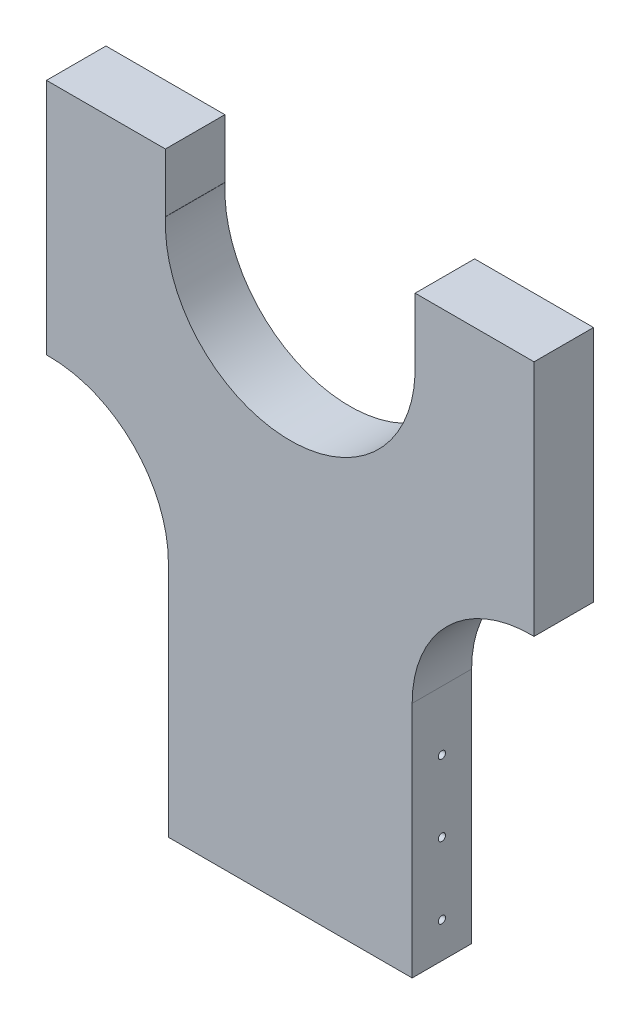
SolidWorks part; units mm, degrees
ref_plane "Front Plane" through (0, 0, 0) normal (0, 0, 1) x (1, 0, 0)
ref_plane "Top Plane" through (0, 0, 0) normal (0, 1, 0) x (1, 0, 0)
ref_plane "Right Plane" through (0, 0, 0) normal (1, 0, 0) x (0, 0, -1)
sketch "Sketch1" plane through (0, 0, 0) normal (0, 0, 1) x (1, 0, 0)
  line L0 (0, 0) -> (0, 99.9478) construction
  line L1 (0, 0) -> (-105.839, 0) construction
  line L2 (-142.7762, 400) -> (240.224, 400) construction
  line L7 (-92.5182, 500) -> (259.2874, 500) construction
  line L8 (-102.5, 485.4345) -> (-102.5, -62.3793) construction
  line L9 (-205, 425.4562) -> (-205, 156.6078) construction
  line L10 (-358.1139, 300) -> (-64.3941, 300) construction
  line L11 (102.5, 0) -> (-102.5, 0)
  line L12 (-102.5, 0) -> (-102.5, 200)
  line L13 (-202.5, 300) -> (-205, 300)
  line L14 (-205, 300) -> (-205, 490)
  line L15 (-195, 500) -> (-112.5, 500)
  line L16 (-102.5, 490) -> (-102.5, 400.25)
  line L17 (-102.25, 400) -> (102.25, 400)
  line L18 (102.5, 490) -> (102.5, 400.25)
  line L19 (195, 500) -> (112.5, 500)
  line L20 (205, 300) -> (205, 490)
  line L21 (202.5, 300) -> (205, 300)
  line L22 (102.5, 0) -> (102.5, 200)
  arc A0 (102.5, 200) -> (202.5, 300) centre (202.5, 200) cw
  arc A1 (-102.5, 200) -> (-202.5, 300) centre (-202.5, 200) ccw
  arc A2 (205, 490) -> (195, 500) centre (195, 490) ccw
  arc A3 (112.5, 500) -> (102.5, 490) centre (112.5, 490) ccw
  arc A4 (-102.5, 490) -> (-112.5, 500) centre (-112.5, 490) ccw
  arc A5 (-195, 500) -> (-205, 490) centre (-195, 490) ccw
  arc A6 (102.25, 400) -> (102.5, 400.25) centre (102.25, 400.25) ccw
  arc A7 (-102.25, 400) -> (-102.5, 400.25) centre (-102.25, 400.25) cw
  point P24 (0, 400)
  point P29 (0, 0)
  point P31 (102.5, 300)
  point P34 (-102.5, 300)
  point P37 (205, 500)
  point P40 (102.5, 500)
  point P43 (-102.5, 500)
  point P46 (-205, 500)
  point P49 (102.5, 400)
  point P52 (-102.5, 400)
  dimension "D6" = 100
  dimension "D7" = 10
  dimension "D8" = 0.25
  dimension "D1" = 400
  dimension "D2" = 100
  dimension "D3" = 102.5
  dimension "D4" = 102.5
  dimension "D5" = 100
extrude "Boss-Extrude2" add sketch "Sketch1" along normal blind 50
sketch "Sketch2" plane through (0, 0, 0) normal (1, 0, 0) x (0, 0, -1)
  line L0 (0, 0) -> (-185.943, 0) construction
  line L1 (0, 0) -> (0, -33.187) construction
  line L2 (-137.4157, 30) -> (59.3527, 30) construction
  line L3 (-134.7567, 60) -> (60.0175, 60) construction
  line L4 (-143.7005, 90) -> (95.8999, 90) construction
  line L5 (-138.1489, 120) -> (60.2857, 120) construction
  line L6 (-100, 469.161) -> (-100, 561.3071) construction
  line L8 (-25, 355.6073) -> (-25, 534.3148) construction
  line L9 (-116.4868, 150) -> (33.8347, 150) construction
  circle A0 centre (-25, 30) radius 3.05
  circle A1 centre (-25, 90) radius 3.05
  circle A2 centre (-25, 150) radius 3.05
  point P2 (0, 0)
  point P26 (0, 0)
  point P27 (0, 0)
  dimension "D8" = 6.1
  dimension "D9" = 6.1
  dimension "D10" = 6.1
  dimension "D1" = 30
  dimension "D2" = 30
  dimension "D3" = 30
  dimension "D4" = 30
  dimension "D5" = 100
  dimension "D6" = 75
  dimension "D7" = 30
sketch "Sketch5" plane through (0, 0, 0) normal (0, 0, 1) x (1, 0, 0)
  line L0 (0, 0) -> (0, 495.9267) construction
  line L1 (0, 0) -> (-201.2141, 0) construction
  line L2 (-102.5, 445.125) -> (213.1937, 445.125) construction
  circle A0 centre (0, 445.125) radius 105
  point P10 (0, 0)
  dimension "D2" = 210
  dimension "D1" = 445.125
sketch "Sketch6" plane through (0, 0, 0) normal (0, 0, 1) x (1, 0, 0)
  line L0 (0, 0) -> (0, 557.0342) construction
  line L1 (202.5, 300) -> (205, 300)
  line L2 (0, 0) -> (-400.078, 0) construction
  line L3 (200000, 0) -> (-200201.2141, 0) construction
  line L4 (-102.5, 0) -> (-102.5, 544.6569) construction
  line L5 (102.5, -39.9884) -> (102.5, 553.3938) construction
  line L6 (-174.3743, 500) -> (295.963, 500) construction
  line L7 (205, 300) -> (205, 500)
  line L8 (-205, 300) -> (266.1119, 300) construction
  line L9 (-205, 480.5862) -> (-205, 206.8295) construction
  line L11 (205, 421.612) -> (205, 62.5629) construction
  line L13 (-102.5, 0) -> (102.5, 0)
  line L14 (102.5, 0) -> (102.5, 200)
  line L17 (205, 500) -> (-205, 500)
  line L18 (-205, 500) -> (-205, 300)
  line L19 (-205, 300) -> (-202.5, 300)
  line L21 (-102.5, 200) -> (-102.5, 0)
  arc A0 (102.5, 200) -> (202.5, 300) centre (202.5, 200) cw
  arc A1 (-102.5, 200) -> (-202.5, 300) centre (-202.5, 200) ccw
  point P25 (102.5, 300)
  point P37 (-102.5, 300)
  dimension "D5" = 100
  dimension "D1" = 102.5
  dimension "D2" = 500
  dimension "D3" = 102.5
  dimension "D4" = 102.5
extrude "Boss-Extrude3" add sketch "Sketch6" along normal blind 50
extrude "Cut-Extrude6" cut sketch "Sketch5" along normal through all
sketch "Sketch8" plane through (0, 0, 0) normal (0, 0, 1) x (1, 0, 0)
  line L0 (0, 0) -> (0, 503.0047) construction
  line L1 (0, 0) -> (-322.5909, 0) construction
  line L2 (-195.6193, 500) -> (250.7474, 500) construction
  line L4 (-105, 445.125) -> (-105, 581.9769) construction
  line L5 (105, 445.125) -> (105, 567.2734) construction
  line L6 (-105, 450.6961) -> (238.3529, 450.6961) construction
  line L8 (-105, 500) -> (105, 500)
  line L11 (-105, 450.6961) -> (105, 450.6961)
  line L12 (-105, 500) -> (-105, 450.6961)
  line L13 (105, 500) -> (105, 450.6961)
  dimension "D1" = 500
  dimension "D2" = 105
  dimension "D3" = 105
  dimension "D4" = 49.3039
extrude "Cut-Extrude7" cut sketch "Sketch8" along normal through all
extrude "Cut-Extrude8" cut sketch "Sketch2" along normal blind 6 from surface starting at face at (-102.5, 100, 25)
extrude "Cut-Extrude9" cut sketch "Sketch2<3>" against normal blind 6 from surface starting at face at (102.5, 100, 25)
sketch "Sketch2<3>" plane through (0, 0, 0) normal (1, 0, 0) x (0, 0, -1) same geometry as "Sketch2"
